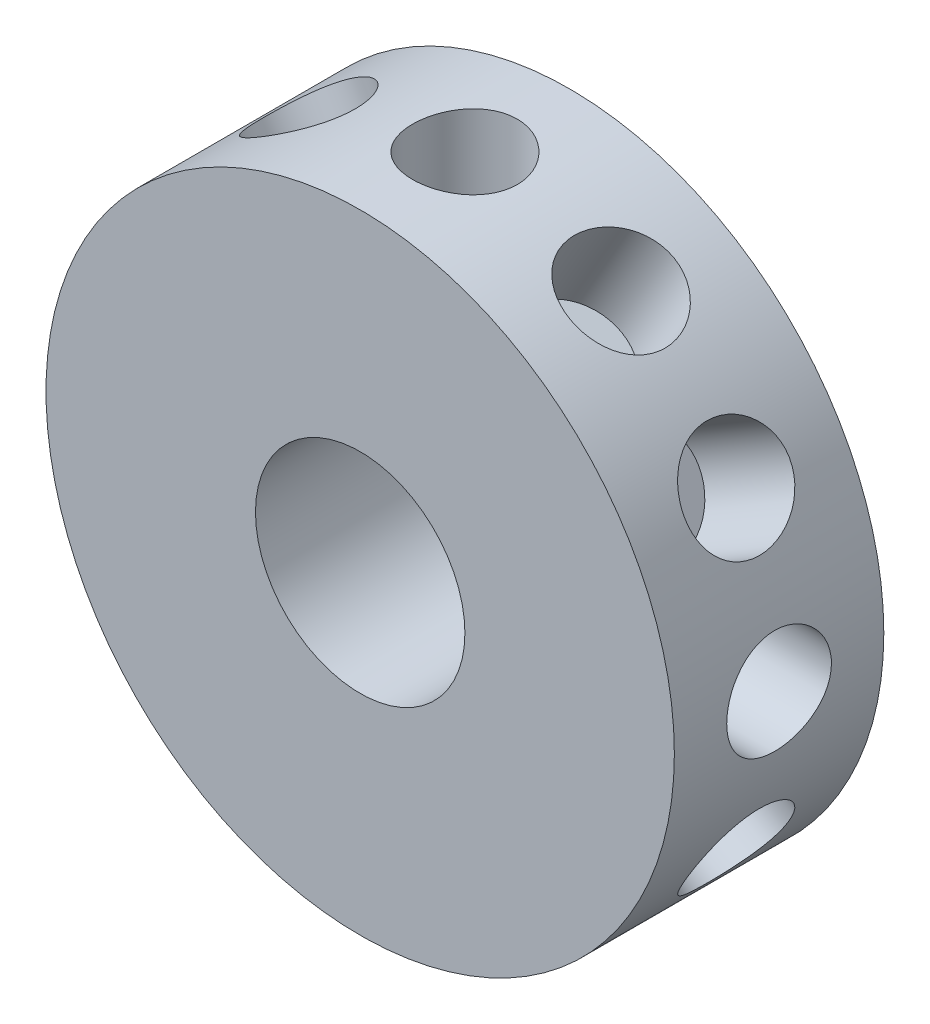
SolidWorks part; units mm, degrees
ref_plane "Front Plane" through (0, 0, 0) normal (0, 0, 1) x (1, 0, 0)
ref_plane "Top Plane" through (0, 0, 0) normal (0, 1, 0) x (1, 0, 0)
ref_plane "Right Plane" through (0, 0, 0) normal (1, 0, 0) x (0, 0, -1)
ref_axis "X" through (-88.99, 0, 0) along (1, 0, 0)
ref_axis "Y" through (0, 55, 0) along (0, -1, 0)
ref_axis "Z" through (0, 0, -88.99) along (0, 0, 1)
sketch "Sketch1" plane through (0, 0, 0) normal (0, 0, 1) x (1, 0, 0)
  circle A0 centre (0, 0) radius 2
  circle A1 centre (0, 0) radius 6
  dimension "D1" = 4
  dimension "D2" = 4
extrude "Boss-Extrude1" add sketch "Sketch1" along normal mid plane 4
ref_plane "Plane1" through (0, -6, 0) normal (0, -1, 0) x (-1, 0, 0)
sketch "Sketch3" plane through (0, -6, 0) normal (0, -1, 0) x (-1, 0, 0)
  circle A0 centre (0, 0) radius 1
  dimension "D1" = 2
extrude "Cut-Extrude1" cut sketch "Sketch3" against normal blind 2
pattern_circular "CirPattern1" count 12 over 360 about axis through (0, 0, -88.99) along (0, 0, 1) of "Cut-Extrude1"
equation "\"Axle Diameter\"= 0.4cm"
equation "\"D1@Sketch1\"=\"Axle Diameter\""
